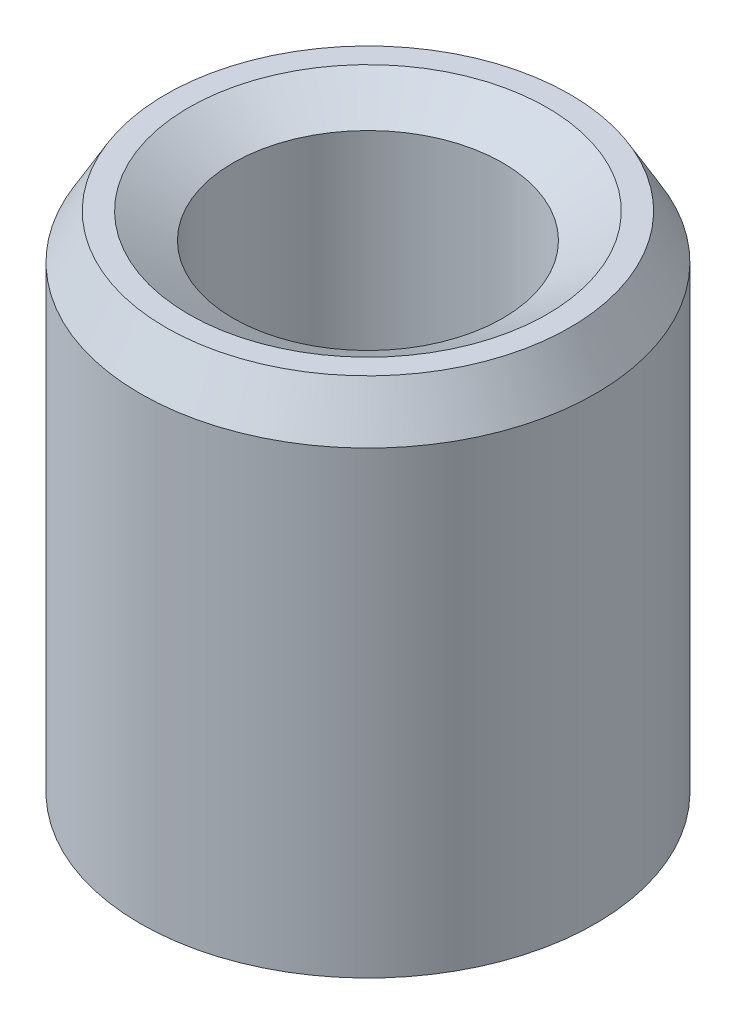
SolidWorks part; units mm, degrees
ref_plane "Front Plane" through (0, 0, 0) normal (0, 0, 1) x (1, 0, 0)
ref_plane "Top Plane" through (0, 0, 0) normal (0, 1, 0) x (1, 0, 0)
ref_plane "Right Plane" through (0, 0, 0) normal (1, 0, 0) x (0, 0, -1)
sketch "Sketch1" plane through (0, 0, 0) normal (0, 1, 0) x (1, 0, 0)
  circle A0 centre (0, 0) radius 17.5
  dimension "SLEEVE_OD" = 35
extrude "Boss-Extrude1" add sketch "Sketch1" along normal blind 40.6651
sketch "Sketch2" plane through (0, 0, 0) normal (0, 1, 0) x (1, 0, 0)
  circle A0 centre (0, 0) radius 10.3566
  dimension "BORE_D" = 20.7132
extrude "Cut-Extrude1" cut sketch "Sketch2" along normal through all
chamfer "Chamfer1" distance 3.4154 angle 30 4 edges at (0, 40.6651, 10.3566) (0, 0, 10.3566) (0, 0, 17.5) (0, 40.6651, 17.5) first distance on face at (0, 40.6651, 10.3566) first distance on face at (0, 0, 10.3566) first distance on face at (0, 40.6651, 17.5)
